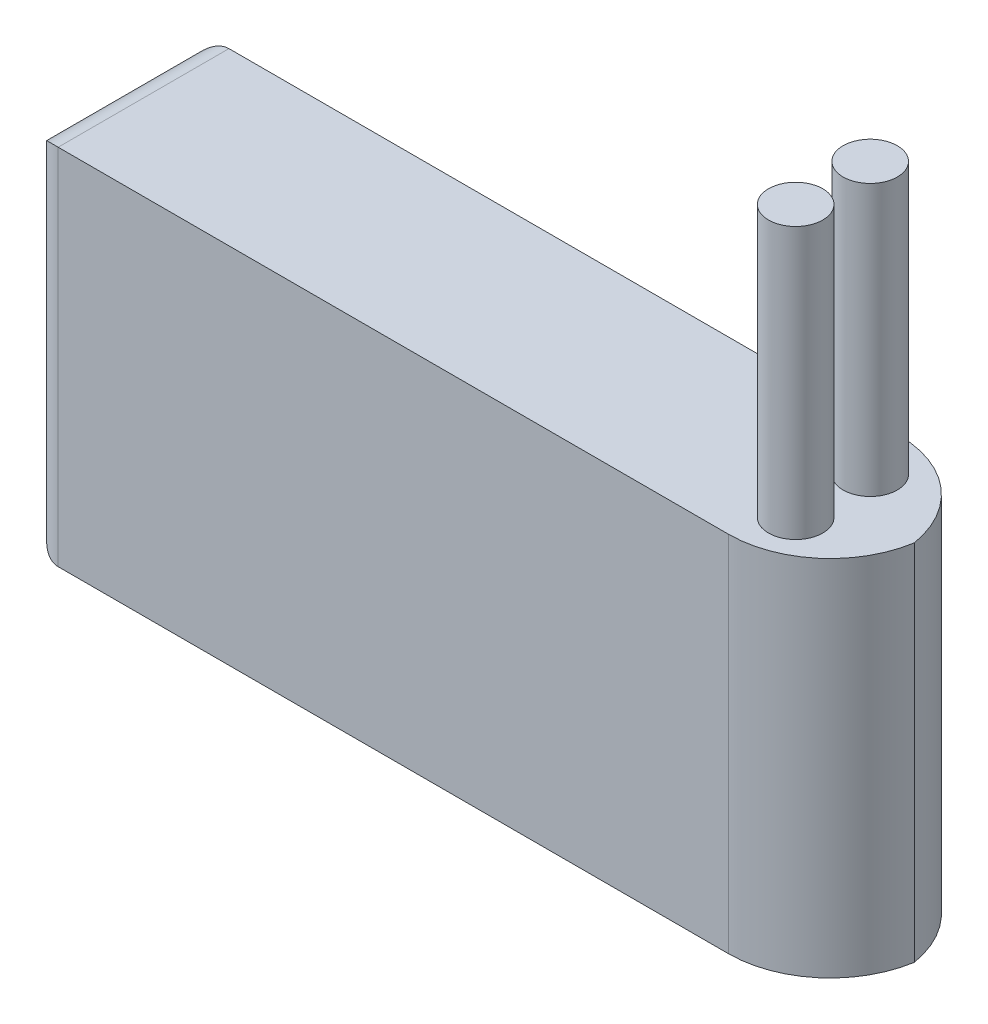
SolidWorks part; units mm, degrees
ref_plane "Front Plane" through (0, 0, 0) normal (0, 0, 1) x (1, 0, 0)
ref_plane "Top Plane" through (0, 0, 0) normal (0, 1, 0) x (1, 0, 0)
ref_plane "Right Plane" through (0, 0, 0) normal (1, 0, 0) x (0, 0, -1)
sketch "Sketch1" plane through (0, 0, 0) normal (0, 0, 1) x (1, 0, 0)
  line L1 (0, 0) -> (74.93, 0)
  line L2 (0, 0) -> (0, 34.036)
  line L3 (0, 34.036) -> (74.93, 34.036)
  line L4 (74.93, 0) -> (74.93, 34.036)
  dimension "D1" = 74.93
  dimension "D2" = 34.036
extrude "Boss-Extrude1" add sketch "Sketch1" along normal blind 16.002
fillet "Fillet1" radius 9.525 2 edges at (74.93, 17.018, 16.002) (74.93, 17.018, 0)
sketch "Sketch2" plane through (0, 34.036, 0) normal (0, 1, 0) x (1, 0, 0)
  line L0 (67.1873, -4.5085) -> (67.1873, -11.4935) construction
  line L1 (67.1873, -8.001) -> (74.8073, -8.001) construction
  circle A0 centre (67.1873, -4.5085) radius 2.54
  circle A1 centre (67.1873, -11.4935) radius 2.54
  dimension "D1" = 5.08
  dimension "D2" = 5.08
  dimension "D3" = 6.985
  dimension "D4" = 7.62
extrude "Boss-Extrude2" add sketch "Sketch2" along normal blind 25.4
fillet "Fillet2" radius 2.6035 4 edges at (0, 34.036, 8.001) (0, 17.018, 16.002) (0, 0, 8.001) (0, 17.018, 0)
